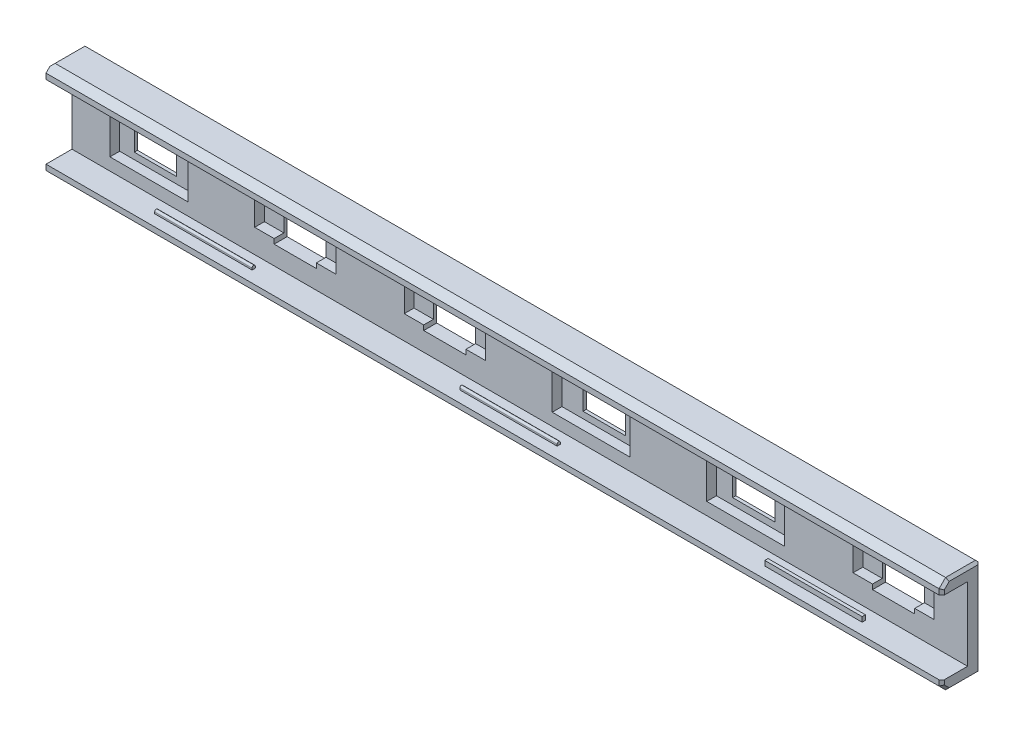
SolidWorks part; units mm, degrees
ref_plane "Front Plane" through (0, 0, 0) normal (0, 0, 1) x (1, 0, 0)
ref_plane "Top Plane" through (0, 0, 0) normal (0, 1, 0) x (1, 0, 0)
ref_plane "Right Plane" through (0, 0, 0) normal (1, 0, 0) x (0, 0, -1)
sketch "Sketch1" plane through (0, 0, 0) normal (0, 0, 1) x (1, 0, 0)
  line L1 (-91.75, 25.6543) -> (46.25, 25.6543)
  line L2 (-91.75, 25.6543) -> (-91.75, 10.6543)
  line L3 (-91.75, 10.6543) -> (46.25, 10.6543)
  line L4 (46.25, 25.6543) -> (46.25, 10.6543)
  dimension "D1" = 138
  dimension "D2" = 15
extrude "Boss-Extrude1" add sketch "Sketch1" along normal blind 6
sketch "Sketch2" plane through (0, 0, 6) normal (0, 0, 1) x (1, 0, 0)
  line L0 (-91.75, 25.6543) -> (-91.75, 10.6543) construction
  line L1 (-83.65, 20.9043) -> (-77.15, 20.9043)
  line L2 (-83.65, 20.9043) -> (-83.65, 15.4043)
  line L3 (-83.65, 15.4043) -> (-77.15, 15.4043)
  line L4 (-77.15, 20.9043) -> (-77.15, 15.4043)
  line L5 (46.25, 25.6543) -> (-91.75, 25.6543) construction
  dimension "D1" = 6.5
  dimension "D2" = 5.5
  dimension "D3" = 8.1
  dimension "D4" = 4.75
extrude "Cut-Extrude1" cut sketch "Sketch2" against normal through all both and the other way through all
sketch "Sketch3" plane through (0, 0, 6) normal (0, 0, 1) x (1, 0, 0)
  line L0 (-77.15, 15.4043) -> (-77.15, 20.9043) construction
  line L1 (-60.6, 20.9043) -> (-54.1, 20.9043)
  line L2 (-60.6, 20.9043) -> (-60.6, 15.4043)
  line L3 (-60.6, 15.4043) -> (-54.1, 15.4043)
  line L4 (-54.1, 20.9043) -> (-54.1, 15.4043)
  dimension "D1" = 6.5
  dimension "D2" = 5.5
  dimension "D3" = 16.55
extrude "Cut-Extrude2" cut sketch "Sketch3" against normal through all both and the other way through all
sketch "Sketch4" plane through (0, 0, 6) normal (0, 0, 1) x (1, 0, 0)
  line L0 (-54.1, 15.4043) -> (-54.1, 20.9043) construction
  line L1 (-37.55, 20.9043) -> (-31.05, 20.9043)
  line L2 (-37.55, 20.9043) -> (-37.55, 15.4043)
  line L3 (-37.55, 15.4043) -> (-31.05, 15.4043)
  line L4 (-31.05, 20.9043) -> (-31.05, 15.4043)
  line L5 (-91.75, 10.6543) -> (46.25, 10.6543) construction
  dimension "D1" = 6.5
  dimension "D2" = 5.5
  dimension "D3" = 16.55
  dimension "D4" = 4.75
extrude "Cut-Extrude3" cut sketch "Sketch4" against normal through all both and the other way through all
sketch "Sketch5" plane through (0, 0, 6) normal (0, 0, 1) x (1, 0, 0)
  line L0 (-31.05, 15.4043) -> (-31.05, 20.9043) construction
  line L1 (-14.5, 20.9043) -> (-8, 20.9043)
  line L2 (-14.5, 20.9043) -> (-14.5, 15.4043)
  line L3 (-14.5, 15.4043) -> (-8, 15.4043)
  line L4 (-8, 20.9043) -> (-8, 15.4043)
  line L6 (8.55, 20.9043) -> (15.05, 20.9043)
  line L7 (8.55, 20.9043) -> (8.55, 15.4043)
  line L8 (8.55, 15.4043) -> (15.05, 15.4043)
  line L9 (15.05, 20.9043) -> (15.05, 15.4043)
  line L10 (31.6, 20.9043) -> (38.1, 20.9043)
  line L11 (31.6, 20.9043) -> (31.6, 15.4043)
  line L12 (31.6, 15.4043) -> (38.1, 15.4043)
  line L13 (38.1, 20.9043) -> (38.1, 15.4043)
  dimension "D1" = 6.5
  dimension "D2" = 5.5
  dimension "D3" = 16.55
  dimension "D4" = 6.5
  dimension "D5" = 6.5
  dimension "D6" = 5.5
  dimension "D7" = 5.5
  dimension "D8" = 16.55
  dimension "D9" = 16.55
extrude "Cut-Extrude4" cut sketch "Sketch5" against normal through all both and the other way through all
sketch "Sketch8" plane through (0, 0, 6) normal (0, 0, 1) x (1, 0, 0)
  line L0 (-91.75, 25.6543) -> (-91.75, 10.6543) construction
  line L1 (46.25, 10.6543) -> (46.25, 25.6543) construction
  line L2 (-91.75, 23.8043) -> (46.25, 23.8043)
  line L3 (-91.75, 23.8043) -> (-91.75, 12.5043)
  line L4 (-91.75, 12.5043) -> (46.25, 12.5043)
  line L5 (46.25, 23.8043) -> (46.25, 12.5043)
  line L6 (46.25, 25.6543) -> (-91.75, 25.6543) construction
  dimension "D1" = 11.3
  dimension "D2" = 1.85
extrude "Cut-Extrude5" cut sketch "Sketch8" against normal blind 4 and the other way through all
sketch "Sketch9" plane through (0, 0, 2) normal (0, 0, 1) x (1, 0, 0)
  line L0 (38.1, 15.4043) -> (31.6, 15.4043) construction
  line L1 (-8, 20.9043) -> (-8, 15.4043) construction
  line L2 (38.1, 20.9043) -> (38.1, 15.4043) construction
  line L3 (-17.75, 21.9043) -> (-5.75, 21.9043)
  line L4 (-17.75, 21.9043) -> (-17.75, 14.4043)
  line L5 (-17.75, 14.4043) -> (-5.75, 14.4043)
  line L6 (-5.75, 21.9043) -> (-5.75, 14.4043)
  line L7 (-91.75, 12.5043) -> (46.25, 12.5043) construction
  line L8 (8.55, 15.4043) -> (8.55, 20.9043) construction
  line L9 (6.05, 21.9043) -> (18.05, 21.9043)
  line L10 (6.05, 21.9043) -> (6.05, 14.4043)
  line L11 (46.25, 12.5043) -> (-91.75, 12.5043) construction
  line L12 (-85.9, 21.9043) -> (-73.9, 21.9043)
  line L13 (-85.9, 21.9043) -> (-85.9, 14.4043)
  line L14 (-85.9, 14.4043) -> (-73.9, 14.4043)
  line L15 (-73.9, 21.9043) -> (-73.9, 14.4043)
  line L16 (-83.65, 15.4043) -> (-83.65, 20.9043) construction
  line L17 (6.05, 14.4043) -> (18.05, 14.4043)
  line L18 (18.05, 21.9043) -> (18.05, 14.4043)
  line L20 (41.1, 20.1543) -> (28.6, 20.1543)
  line L21 (41.1, 20.1543) -> (41.1, 16.1543)
  line L22 (41.1, 16.1543) -> (28.6, 16.1543)
  line L23 (28.6, 20.1543) -> (28.6, 16.1543)
  dimension "D1" = 2.25
  dimension "D2" = 12
  dimension "D3" = 7.5
  dimension "D4" = 1.9
  dimension "D5" = 12
  dimension "D6" = 7.5
  dimension "D7" = 1.9
  dimension "D8" = 2.25
  dimension "D9" = 12
  dimension "D10" = 2.5
  dimension "D11" = 7.5
  dimension "D12" = 4
  dimension "D13" = 12.5
  dimension "D14" = 0.75
  dimension "D15" = 3
extrude "Cut-Extrude6" cut sketch "Sketch9" against normal blind 1.5
sketch "Sketch10" plane through (0, 0, 2) normal (0, 0, 1) x (1, 0, 0)
  line L1 (-40.55, 20.1543) -> (-28.05, 20.1543)
  line L2 (-40.55, 20.1543) -> (-40.55, 16.1543)
  line L3 (-40.55, 16.1543) -> (-28.05, 16.1543)
  line L4 (-28.05, 20.1543) -> (-28.05, 16.1543)
  line L5 (-63.6, 20.1543) -> (-51.1, 20.1543)
  line L6 (-63.6, 20.1543) -> (-63.6, 16.1543)
  line L7 (-63.6, 16.1543) -> (-51.1, 16.1543)
  line L8 (-51.1, 20.1543) -> (-51.1, 16.1543)
  line L9 (-60.6, 15.4043) -> (-60.6, 20.9043) construction
  line L10 (-54.1, 20.9043) -> (-54.1, 15.4043) construction
  line L11 (-54.1, 15.4043) -> (-60.6, 15.4043) construction
  line L13 (-37.55, 15.4043) -> (-37.55, 20.9043) construction
  line L15 (-31.05, 15.4043) -> (-37.55, 15.4043) construction
  dimension "D1" = 3
  dimension "D2" = 3
  dimension "D3" = 4
  dimension "D4" = 0.75
  dimension "D5" = 12.5
  dimension "D6" = 3
  dimension "D7" = 4
  dimension "D8" = 0.75
extrude "Cut-Extrude7" cut sketch "Sketch10" against normal blind 1.5
sketch "Sketch12" plane through (46.25, 0, 0) normal (1, 0, 0) x (0, 0, -1)
  line L0 (-6, 25.6543) -> (-6, 24.6543)
  line L1 (-6, 23.8043) -> (-6, 25.6543) construction
  line L2 (-6, 24.6543) -> (-5, 25.6543)
  line L3 (-6, 25.6543) -> (0, 25.6543) construction
  line L4 (-5, 25.6543) -> (-6, 25.6543)
  line L5 (-6, 10.6543) -> (-5, 10.6543)
  line L6 (-6, 10.6543) -> (0, 10.6543) construction
  line L7 (-5, 10.6543) -> (-6, 11.6543)
  line L8 (-6, 10.6543) -> (-6, 12.5043) construction
  line L9 (-6, 11.6543) -> (-6, 10.6543)
  dimension "D1" = 1
  dimension "D2" = 1
  dimension "D3" = 1
extrude "Cut-Extrude8" cut sketch "Sketch12" against normal up to surface (138 mm away) up to face at (-91.75, 18.1543, 3.5)
sketch "Sketch13" plane through (0, 0, 0) normal (0, 0, -1) x (-1, 0, 0)
  line L0 (91.75, 25.6543) -> (91.75, 10.6543) construction
  line L1 (89.25, 23.1543) -> (89.75, 23.1543)
  line L2 (89.25, 23.1543) -> (89.25, 13.1543)
  line L3 (89.25, 13.1543) -> (89.75, 13.1543)
  line L4 (89.75, 23.1543) -> (89.75, 13.1543)
  line L5 (-46.25, 25.6543) -> (91.75, 25.6543) construction
  dimension "D1" = 2
  dimension "D2" = 0.5
  dimension "D3" = 10
  dimension "D4" = 2.5
extrude "Cut-Extrude9" cut sketch "Sketch13" against normal blind 0.6
fillet "Fillet1" radius 0.25 1 edges at (-89.75, 18.1543, 0)
fillet "Fillet2" radius 0.25 4 edges at (-89.5, 23.1543, 0.6) (-89.75, 18.1543, 0.6) (-89.5, 13.1543, 0.6) (-89.25, 18.1543, 0.6)
sketch "Sketch16" plane through (0, 23.8043, 0) normal (0, -1, 0) x (1, 0, 0)
  line L0 (-91.75, 6) -> (46.25, 6) construction
  line L1 (-61.75, 4.25) -> (-76.75, 4.25)
  line L2 (-61.75, 4.25) -> (-61.75, 3.75)
  line L3 (-61.75, 3.75) -> (-76.75, 3.75)
  line L4 (-76.75, 4.25) -> (-76.75, 3.75)
  line L5 (-91.75, 6) -> (-91.75, 2) construction
  dimension "D1" = 15
  dimension "D2" = 0.5
  dimension "D3" = 1.75
  dimension "D4" = 15
extrude "Boss-Extrude2" add sketch "Sketch16" along normal blind 0.75
fillet "Fillet3" radius 0.5 1 edges at (-69.25, 23.0543, 4.25)
fillet "Fillet4" radius 0.25 1 edges at (-69.25, 23.0543, 3.75)
sketch "Sketch17" plane through (0, 12.5043, 0) normal (0, 1, 0) x (1, 0, 0)
  line L0 (-91.75, -6) -> (-91.75, -2) construction
  line L1 (-61.75, -3.75) -> (-76.75, -3.75)
  line L2 (-61.75, -3.75) -> (-61.75, -4.25)
  line L3 (-61.75, -4.25) -> (-76.75, -4.25)
  line L4 (-76.75, -3.75) -> (-76.75, -4.25)
  line L5 (46.25, -6) -> (-91.75, -6) construction
  dimension "D1" = 15
  dimension "D2" = 0.5
  dimension "D3" = 15
  dimension "D4" = 1.75
extrude "Boss-Extrude3" add sketch "Sketch17" along normal blind 0.75
fillet "Fillet5" radius 0.5 1 edges at (-69.25, 13.2543, 4.25)
fillet "Fillet6" radius 0.25 1 edges at (-69.25, 13.2543, 3.75)
pattern_linear "LPattern1" count 3 spacing 47 along (1, 0, 0) of "Boss-Extrude3"
pattern_linear "LPattern2" count 3 spacing 47 along (1, 0, 0) of "Boss-Extrude2"
fillet "Fillet7" radius 0.5 1 edges at (-22.25, 23.0543, 4.25)
fillet "Fillet8" radius 0.25 1 edges at (-22.25, 23.0543, 3.75)
fillet "Fillet9" radius 0.5 1 edges at (-22.25, 13.2543, 4.25)
fillet "Fillet10" radius 0.25 1 edges at (-22.25, 13.2543, 3.75)
chamfer "Chamfer1" distance 0.4 angle 45 2 edges at (-22.75, 10.6543, 0) (-22.75, 25.6543, 0)
chamfer "Chamfer2" distance 0.4 angle 45 2 edges at (46.25, 18.1543, 0) (-91.75, 18.1543, 0)
chamfer "Chamfer3" distance 0.4 angle 45 2 edges at (-91.75, 10.6543, 2.7) (-91.75, 25.6543, 2.7)
chamfer "Chamfer5" distance 0.4 angle 45 6 edges at (46.25, 24.2293, 6) (46.25, 25.1543, 5.5) (46.25, 25.6543, 2.7) (46.25, 12.0793, 6) (46.25, 11.1543, 5.5) (46.25, 10.6543, 2.7)
